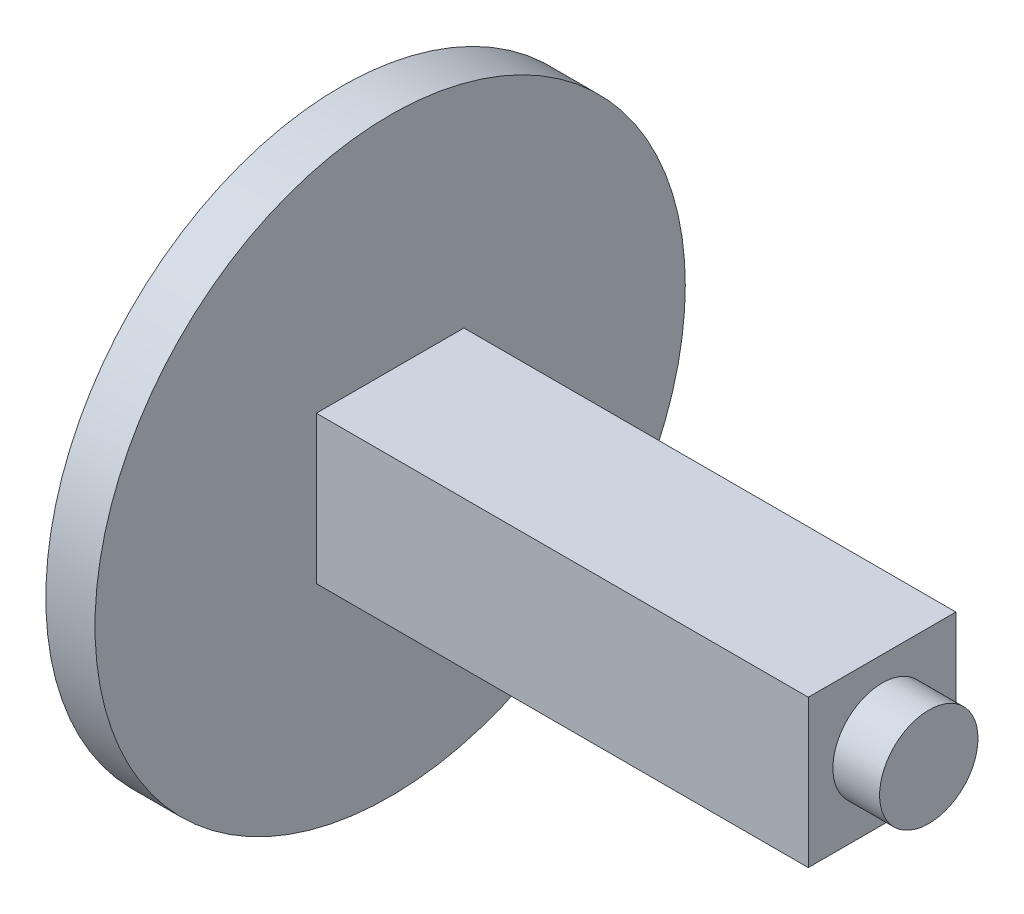
SolidWorks part; units mm, degrees
ref_plane "Plan de face" through (0, 0, 0) normal (0, 0, 1) x (1, 0, 0)
ref_plane "Plan de dessus" through (0, 0, 0) normal (0, 1, 0) x (1, 0, 0)
ref_plane "Plan de droite" through (0, 0, 0) normal (1, 0, 0) x (0, 0, -1)
sketch "Esquisse1" plane through (0, 0, 0) normal (1, 0, 0) x (0, 0, -1)
  circle A0 centre (0, 0) radius 600
  dimension "D1" = 1200
extrude "Boss.-Extru.1" add sketch "Esquisse1" along normal blind 100
sketch "Esquisse2" plane through (100, 0, 0) normal (1, 0, 0) x (0, 0, -1)
  line L1 (-150, -150) -> (150, -150)
  line L2 (-150, -150) -> (-150, 150)
  line L3 (-150, 150) -> (150, 150)
  line L4 (150, -150) -> (150, 150)
  line L5 (-150, -150) -> (150, 150) construction
  line L6 (-150, 150) -> (150, -150) construction
  point P0 (0, 0)
  dimension "D1" = 300
  dimension "D2" = 300
extrude "Boss.-Extru.2" add sketch "Esquisse2" along normal blind 1000
sketch "Esquisse3" plane through (1100, 0, 0) normal (1, 0, 0) x (0, 0, -1)
  circle A0 centre (0, 0) radius 100
extrude "Boss.-Extru.3" add sketch "Esquisse3" along normal blind 95
